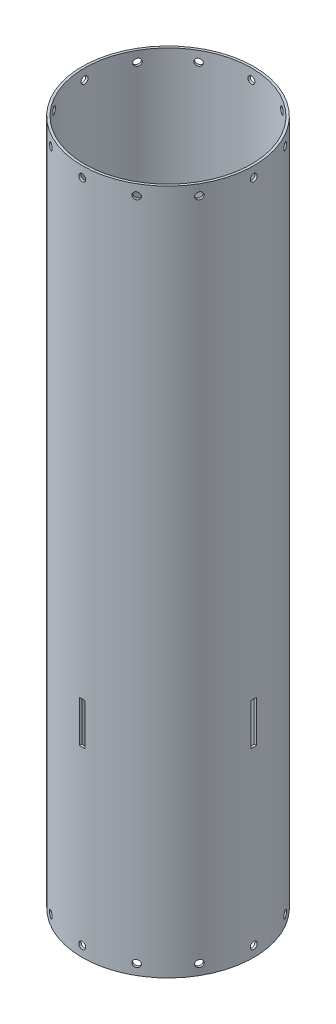
SolidWorks part; units mm, degrees
material "Fiberglass"
ref_plane "Front Plane" through (0, 0, 0) normal (0, 0, 1) x (1, 0, 0)
ref_plane "Top Plane" through (0, 0, 0) normal (0, 1, 0) x (1, 0, 0)
ref_plane "Right Plane" through (0, 0, 0) normal (1, 0, 0) x (0, 0, -1)
sketch "Sketch1" plane through (0, 0, 0) normal (0, 1, 0) x (1, 0, 0)
  circle A0 centre (0, 0) radius 76.2
  circle A1 centre (0, 0) radius 78.359
  dimension "D1" = 152.4
  dimension "D2" = 156.718
extrude "Boss-Extrude1" add sketch "Sketch1" along normal blind 626.11
sketch "Sketch2" plane through (0, 0, 0) normal (0, 0, 1) x (1, 0, 0)
  line L0 (0, 0) -> (0, 105.6712) construction
  line L1 (-76.2, 0) -> (76.2, 0) construction
  line L2 (-78.359, 0) -> (78.359, 0) construction
  line L3 (78.359, 313.055) -> (42.8908, 313.055) construction
  line L4 (78.359, 0) -> (78.359, 626.11) construction
  circle A0 centre (0, 9.525) radius 3.175
  circle A1 centre (0, 616.585) radius 3.175
  dimension "D1" = 6.35
  dimension "D2" = 9.525
extrude "Cut-Extrude1" cut sketch "Sketch2" against normal through all
ref_axis "Axis1" through (0, 0, 0) along (0, 1, 0)
pattern_circular "CirPattern1" count 12 over 360 about axis through (0, 0, 0) along (0, 1, 0) of "Cut-Extrude1" reverse direction yes
sketch "Sketch3" plane through (0, 0, 0) normal (0, 0, 1) x (1, 0, 0)
  line L0 (0, 0) -> (0, 105.6712) construction
  line L1 (-2.54, 166.37) -> (2.54, 166.37)
  line L2 (-2.54, 166.37) -> (-2.54, 204.47)
  line L3 (-2.54, 204.47) -> (2.54, 204.47)
  line L4 (2.54, 166.37) -> (2.54, 204.47)
  line L5 (-2.54, 166.37) -> (2.54, 204.47) construction
  line L6 (-2.54, 204.47) -> (2.54, 166.37) construction
  line L7 (-76.2, 0) -> (76.2, 0) construction
  line L8 (0, 626.11) -> (0, 408.1695) construction
  line L9 (76.2, 626.11) -> (-76.2, 626.11) construction
  point P0 (0, 185.42)
  dimension "D1" = 166.37
  dimension "D2" = 38.1
  dimension "D3" = 5.08
extrude "Cut-Extrude2" cut sketch "Sketch3" against normal through all
ref_axis "Axis2" through (0, 626.11, 0) along (0, -1, 0)
pattern_circular "CirPattern2" count 4 over 360 about axis through (0, 626.11, 0) along (0, -1, 0) of "Cut-Extrude2"
